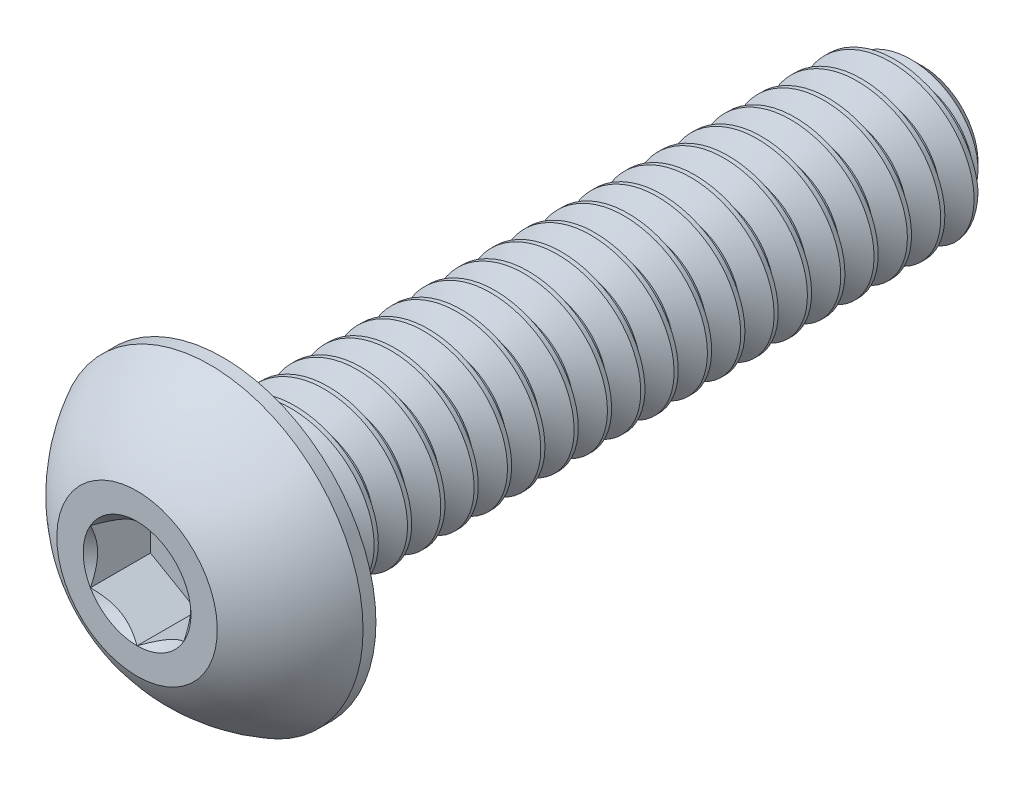
SolidWorks part; units mm, degrees
ref_plane "Front" through (0, 0, 0) normal (0, 0, 1) x (1, 0, 0)
ref_plane "Top" through (0, 0, 0) normal (0, 1, 0) x (1, 0, 0)
ref_plane "Right" through (0, 0, 0) normal (1, 0, 0) x (0, 0, -1)
sketch "Sketch1" plane through (0, 0, 0) normal (1, 0, 0) x (0, 0, -1)
  line L2 (1.1684, 1.0922) -> (10.6934, 1.0922)
  line L3 (10.6934, 1.0922) -> (10.6934, 0)
  line L4 (10.6934, 0) -> (1.1684, 0)
  line L6 (0.9931, 2.0828) -> (1.1684, 2.0828) construction
  line L7 (10.6934, 1.0922) -> (10.6934, -1.0922) construction
  line L8 (0, 0) -> (1.1684, 0) construction
  line L9 (1.1684, 2.0828) -> (1.1684, -2.0828) construction
  line L11 (1.1684, 1.0922) -> (1.1684, 0)
  line L13 (0, 0.635) -> (0, -0.635) construction
  line L14 (0, 0.635) -> (0, 1.0922) construction
  arc A3 (0, 1.0922) -> (0.9931, 2.0828) centre (2.08, 0) cw construction
  dimension "D1" = 0.1753
  dimension "Head Ht" = 1.1684
  dimension "Head Dia" = 4.1656
  dimension "Dia" = 2.1844
  dimension "Lg" = 9.525
  dimension "Hex" = 1.27
revolve "Revolve1" add sketch "Sketch1" angle 360 mid plane about L4
sketch "Sketch3" plane through (0, 0, -10.6934) normal (0, 0, -1) x (-1, 0, 0)
  circle A0 centre (0, 0) radius 1.0922
curve "Helix/Spiral1" pitch 0.4536 height 10.6934 radius 1.0922 centre (0, 0, -10.6934) axis (0, 0, 1) start towards (0, 1, 0)
sketch "Sketch2" plane through (0, 0, 0) normal (1, 0, 0) x (0, 0, -1)
  line L0 (10.6934, 1.0922) -> (11.0903, 1.0922)
  line L1 (11.0903, 1.0922) -> (10.9202, 0.7976)
  line L2 (10.9202, 0.7976) -> (10.8635, 0.7976)
  line L3 (10.8635, 0.7976) -> (10.6934, 1.0922)
  line L4 (10.7784, 0.9449) -> (11.0052, 0.9449) construction
  dimension "D1" = 60
  dimension "D2" = 0.0567
  dimension "D3" = 0.2268
chamfer "Chamfer1" distance 0.3402 angle 45 1 edges at (0, 1.0922, -10.6934)
sweep "Cut-Sweep1" cut profiles "Sketch2" path "Helix/Spiral1"
sketch "Sketch7" plane through (0, 0, 0) normal (1, 0, 0) x (0, 0, -1)
  line L6 (0.9931, 2.0828) -> (1.1684, 2.0828) construction
  line L8 (0, 0) -> (1.1684, 0) construction
  line L11 (1.1684, 2.0828) -> (1.1684, -2.0828) construction
  line L12 (0.9931, 2.0828) -> (1.1684, 2.0828)
  line L13 (0, 0) -> (1.1684, 0)
  line L14 (0, 0.635) -> (0, -0.635) construction
  line L15 (1.1684, 2.0828) -> (1.1684, 0)
  line L16 (0, 1.0922) -> (0, 0)
  arc A2 (0.9931, 2.0828) -> (0, 1.0922) centre (2.08, 0) ccw construction
  arc A3 (0.9931, 2.0828) -> (0, 1.0922) centre (2.08, 0) ccw
revolve "Revolve2" add sketch "Sketch7" angle 360 mid plane about L13
sketch "Sketch5" plane through (0, 0, 0) normal (0, 0, 1) x (1, 0, 0)
  line L1 (0.635, -0.3666) -> (0.635, 0.3666)
  line L2 (0.635, 0.3666) -> (0, 0.7332)
  line L3 (0, 0.7332) -> (-0.635, 0.3666)
  line L4 (-0.635, 0.3666) -> (-0.635, -0.3666)
  line L5 (-0.635, -0.3666) -> (0, -0.7332)
  line L6 (0, -0.7332) -> (0.635, -0.3666)
  circle A0 centre (0, 0) radius 0.635 construction
extrude "Cut-Extrude2" cut sketch "Sketch5" against normal blind 0.8179
sketch "Sketch6" plane through (0, 0, 0) normal (0, 0, 1) x (1, 0, 0)
  circle A0 centre (0, 0) radius 0.7332
extrude "Cut-Extrude3" cut sketch "Sketch6" against normal blind 0.8179 draft 45
sketch "Sketch9" [suppressed] plane through (0, 0, -8.2296) normal (0, 0, 1) x (1, 0, 0)
  circle A2 centre (0, 0) radius 7.9375
extrude "Boss-Extrude2" [suppressed] add sketch "Sketch9" against normal offset from surface (25.4 mm away) 22.225 up to face at (0, 0.752, -10.6934)
sketch "Sketch10" plane through (0, 0, 0) normal (1, 0, 0) x (0, 0, -1)
  line L0 (10.6934, 1.0922) -> (10.6934, -1.0922) construction
  point P0 (10.013, -1.0922)
  dimension "D1" = 0.6804
equation "\"D3@Helix/Spiral1\" = \"Lg@Sketch1\" + \"Head Ht@Sketch1\""
equation "\"D2@Sketch2\" = \"D4@Helix/Spiral1\" * .125"
equation "\"D3@Sketch2\" = \"D4@Helix/Spiral1\" * .5"
equation "\"D1@Chamfer1\" = \"D4@Helix/Spiral1\" * .75"
equation "\"D1@Cut-Extrude2\" = \"Head Ht@Sketch1\" * .7"
equation "\"D1@Sketch1\" = \"Head Ht@Sketch1\" * .15"
equation "\"D1@Sketch10\" = \"D4@Helix/Spiral1\" * 1.5"
equation "\"D1@Cut-Extrude3\" = \"D1@Cut-Extrude2\""
